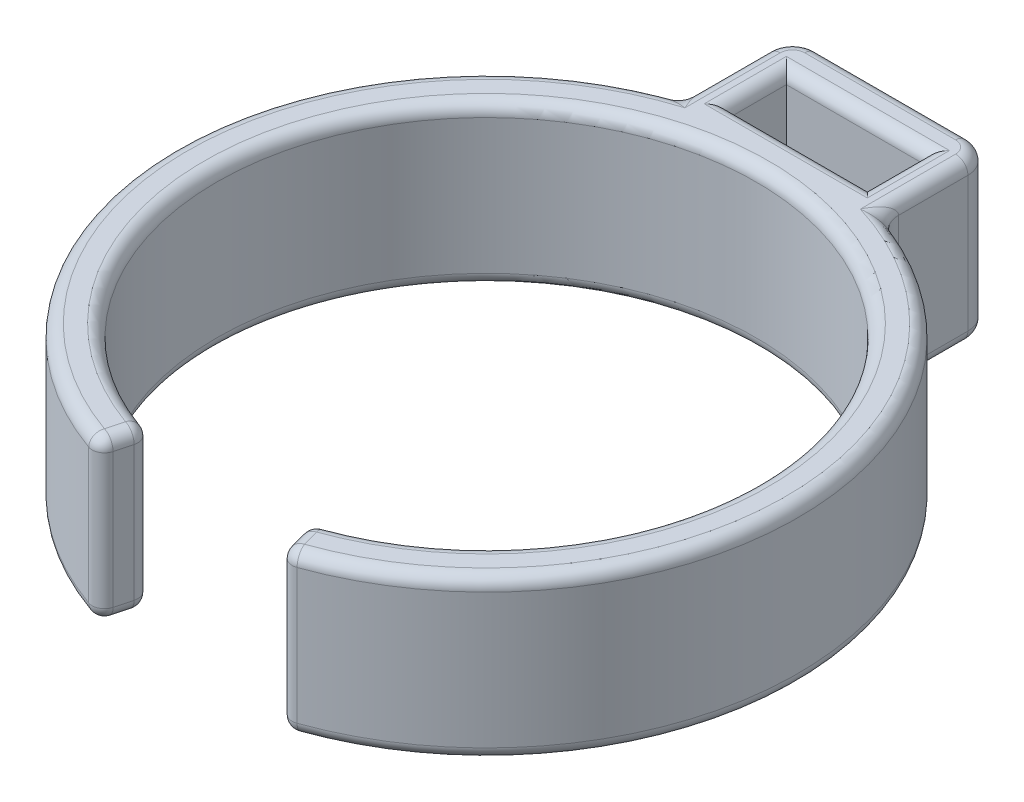
SolidWorks part; units mm, degrees
ref_plane "Front Plane" through (0, 0, 0) normal (0, 0, 1) x (1, 0, 0)
ref_plane "Top Plane" through (0, 0, 0) normal (0, 1, 0) x (1, 0, 0)
ref_plane "Right Plane" through (0, 0, 0) normal (1, 0, 0) x (0, 0, -1)
sketch "Sketch1" plane through (0, 0, 0) normal (0, 1, 0) x (1, 0, 0)
  line L0 (-3.2933, -10.4954) -> (-3.7337, -12.1388)
  line L5 (3.2933, -10.4954) -> (3.7337, -12.1388)
  line L6 (0, 0) -> (0, -12.244) construction
  arc A0 (3.7337, -12.1388) -> (-3.7337, -12.1388) centre (0, 0) ccw
  arc A1 (3.2933, -10.4954) -> (-3.2933, -10.4954) centre (0, 0) ccw
  dimension "D3" = 11
  dimension "D1" = 1.7
  dimension "D2" = 30
extrude "Boss-Extrude1" add sketch "Sketch1" along normal blind 6.5
ref_plane "Plane1" through (0, 0, -12.7) normal (0, 0, -1) x (-1, 0, 0)
sketch "Sketch2" plane through (0, 0, -12.7) normal (0, 0, -1) x (-1, 0, 0)
  line L0 (12.7, 6.5) -> (-12.7, 6.5) construction
  line L1 (4.075, 0) -> (-4.075, 0)
  line L2 (4.075, 0) -> (4.075, 6.5)
  line L3 (4.075, 6.5) -> (-4.075, 6.5)
  line L4 (-4.075, 0) -> (-4.075, 6.5)
  line L5 (4.075, 0) -> (-4.075, 6.5) construction
  line L6 (4.075, 6.5) -> (-4.075, 0) construction
  line L7 (-12.7, 0) -> (12.7, 0) construction
  point P0 (0, 3.25)
  dimension "D1" = 8.15
extrude "Boss-Extrude2" add sketch "Sketch2" against normal up to surface (0.6858 mm away) up to face at (0, 3.25, -0.2806)
sketch "Sketch3" plane through (0, 0, -12.7) normal (0, 0, -1) x (-1, 0, 0)
  line L0 (-4.075, 0) -> (4.075, 0) construction
  line L1 (-4.075, 6.5) -> (-2.825, 6.5)
  line L2 (-4.075, 6.5) -> (-4.075, 0)
  line L3 (-4.075, 0) -> (-2.825, 0)
  line L4 (-2.825, 6.5) -> (-2.825, 0)
  line L5 (4.075, 6.5) -> (-4.075, 6.5) construction
  line L6 (4.075, 0) -> (2.825, 0)
  line L7 (4.075, 0) -> (4.075, 6.5)
  line L8 (4.075, 6.5) -> (2.825, 6.5)
  line L9 (2.825, 0) -> (2.825, 6.5)
  dimension "D1" = 1.25
extrude "Boss-Extrude3" add sketch "Sketch3" along normal blind 2.35
sketch "Sketch4" plane through (0, 0, -15.05) normal (0, 0, -1) x (-1, 0, 0)
  line L0 (4.075, 0) -> (4.075, 6.5) construction
  line L1 (-4.075, 6.5) -> (-4.075, 0) construction
  line L2 (4.075, 0) -> (4.075, 6.5)
  line L3 (-4.075, 6.5) -> (-4.075, 0)
  line L4 (-4.075, 6.5) -> (4.075, 6.5)
  line L5 (-4.075, 0) -> (4.075, 0)
extrude "Boss-Extrude4" add sketch "Sketch4" along normal blind 1.5
fillet "Fillet1" radius 0.5 24 edges at (12.6987, 0, 0.1794) (4.075, 0, -14.2892) (0, 0, -16.55) (-4.075, 0, -14.2892) (-12.6987, 0, 0.1794) (-3.5135, 0, 11.3171) (0, 0, -11) (-2.825, 6.5, -13.875) (0, 6.5, -12.7) (2.825, 6.5, -13.875) (0, 6.5, -15.05) (12.6987, 6.5, 0.1794) (0, 6.5, -11) (-3.5135, 6.5, 11.3171) (-12.6987, 6.5, 0.1794) (-4.075, 6.5, -14.2892) (0, 6.5, -16.55) (4.075, 6.5, -14.2892) (3.2933, 3.25, 10.4954) (3.5135, 6.5, 11.3171) (3.7337, 3.25, 12.1388) (3.5135, 0, 11.3171) (-3.7337, 3.25, 12.1388) (-3.2933, 3.25, 10.4954)
fillet "Fillet2" radius 1 12 edges at (3.9286, 0.1464, -16.4036) (3.9286, 6.3536, -16.4036) (-3.9286, 6.3536, -16.4036) (-3.9286, 0.1464, -16.4036) (3.9057, 6.375, -11.9065) (3.9057, 0.125, -11.9065) (-3.9057, 0.125, -11.9065) (-3.9057, 6.375, -11.9065) (-4.075, 3.25, -16.55) (4.075, 3.25, -16.55) (4.075, 3.25, -12.0285) (-4.075, 3.25, -12.0285)
equation "\"D\" = 22"
equation "\"D3@Sketch1\"=\"D\"/2"
